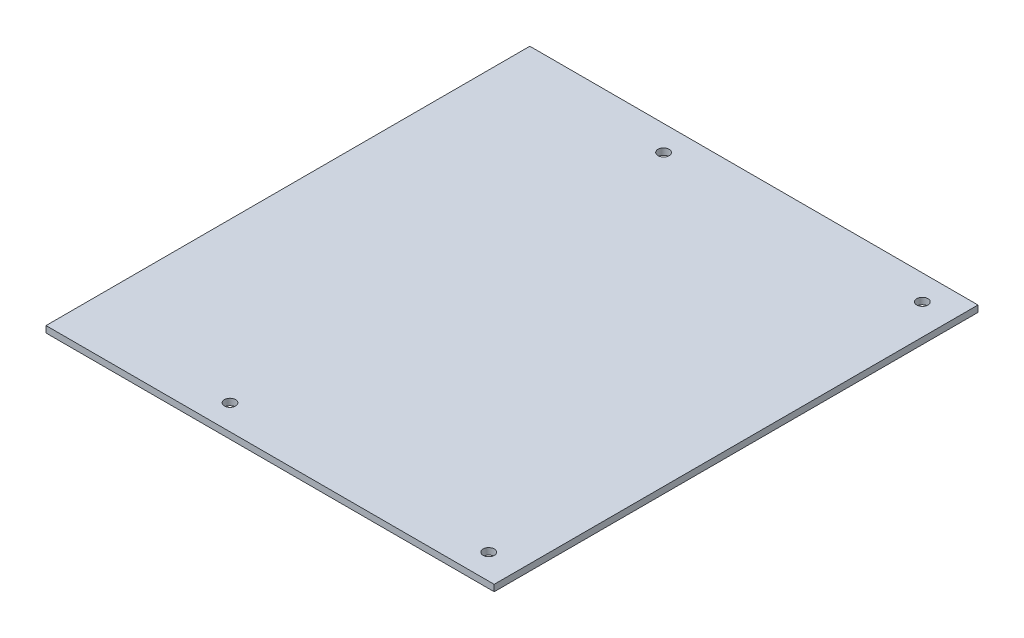
SolidWorks part; units mm, degrees
ref_plane "Front Plane" through (0, 0, 0) normal (0, 0, 1) x (1, 0, 0)
ref_plane "Top Plane" through (0, 0, 0) normal (0, 1, 0) x (1, 0, 0)
ref_plane "Right Plane" through (0, 0, 0) normal (1, 0, 0) x (0, 0, -1)
sketch "Sketch1" plane through (0, 0, 0) normal (0, 1, 0) x (1, 0, 0)
  line L1 (110, -118.75) -> (-110, -118.75)
  line L2 (110, -118.75) -> (110, 118.75)
  line L3 (110, 118.75) -> (-110, 118.75)
  line L4 (-110, -118.75) -> (-110, 118.75)
  line L5 (110, -118.75) -> (-110, 118.75) construction
  line L6 (110, 118.75) -> (-110, -118.75) construction
  point P0 (0, 0)
  dimension "D1" = 237.5
  dimension "D2" = 220
extrude "Boss-Extrude1" add sketch "Sketch1" along normal mid plane 3.175
hole_wizard "M5 Clearance Hole1" positions "Sketch4" profile "Sketch3" hole size "M5" standard "ANSI Metric" end condition through all
sketch "Sketch4" plane through (0, 1.5875, 0) normal (0, 1, 0) x (1, 0, 0)
  line L0 (95, 106.425) -> (95, -106.425) construction
  line L1 (95, -106.425) -> (-32, -106.425) construction
  line L3 (110, -118.75) -> (110, 118.75) construction
  point P0 (-32, 106.425)
  point P2 (95, 106.425)
  point P4 (95, -106.425)
  point P6 (-32, -106.425)
  point P15 (95, 0)
  dimension "D1" = 212.85
  dimension "D2" = 15
  dimension "D3" = 127
sketch "Sketch3" plane through (-32, 1.5875, -106.425) normal (1, 0, 0) x (0, 0, 1)
  line L0 (0, 0) -> (0, 3.175)
  line L1 (0, 3.175) -> (2.75, 3.175)
  line L2 (2.75, 3.175) -> (2.75, 0)
  line L5 (2.75, 0) -> (0, 0)
  line L11 (0, -6.35) -> (0, 107.95) construction
  dimension "Thru Hole Dia." = 5.5
  dimension "Thru Hole Depth" = 3.175
